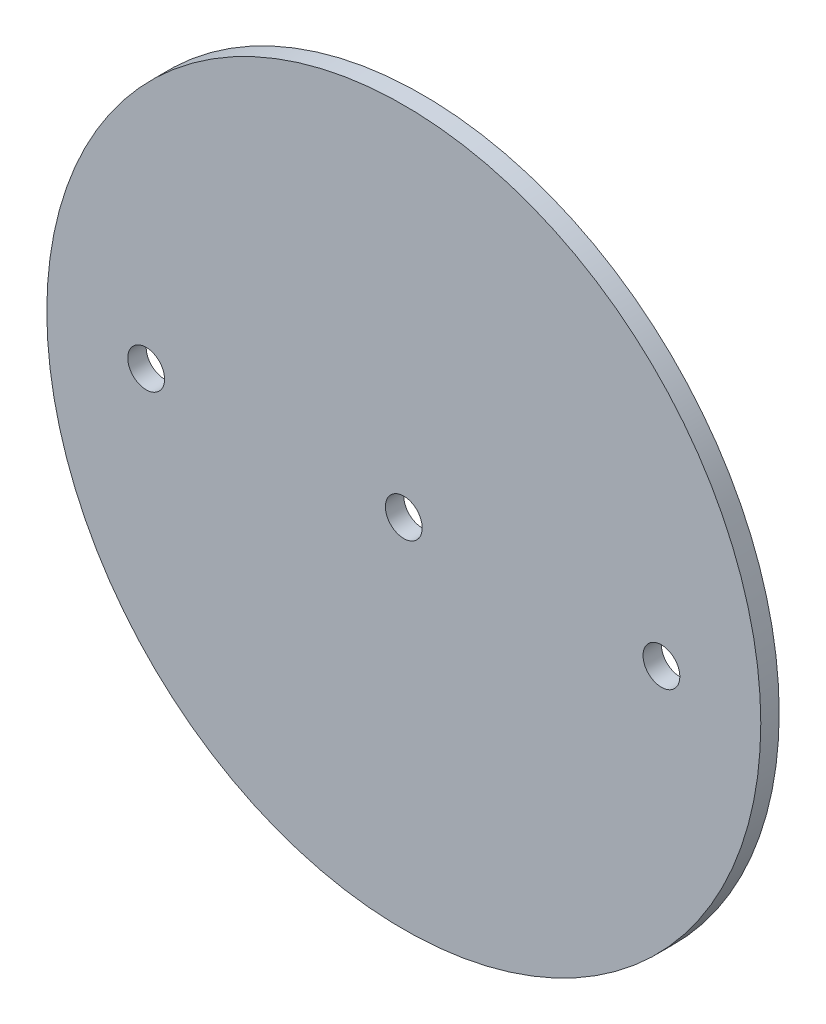
SolidWorks part; units mm, degrees
ref_plane "Front Plane" through (0, 0, 0) normal (0, 0, 1) x (1, 0, 0)
ref_plane "Top Plane" through (0, 0, 0) normal (0, 1, 0) x (1, 0, 0)
ref_plane "Right Plane" through (0, 0, 0) normal (1, 0, 0) x (0, 0, -1)
sketch "Sketch1" plane through (0, 0, 0) normal (0, 0, 1) x (1, 0, 0)
  circle A0 centre (0, 0) radius 61.595
  dimension "D1" = 123.19
extrude "Boss-Extrude1" add sketch "Sketch1" along normal mid plane 3.175
sketch "Sketch2" plane through (0, 0, 1.5875) normal (0, 0, 1) x (1, 0, 0)
  line L0 (-1000, 0) -> (49000, 0) construction
  point P1 (0, 0)
  point P4 (44.45, 0)
  point P5 (-44.45, 0)
  dimension "D1" = 44.45
  dimension "D2" = 88.9
hole_wizard "1/4 (0.25) Diameter Hole1" positions "Sketch2" profile "Sketch3" hole size "1/4" standard "ANSI Inch" end condition through all
sketch "Sketch3" plane through (-44.45, 0, 1.5875) normal (1, 0, 0) x (0, -1, 0)
  line L0 (0, 0) -> (0, 3.175)
  line L1 (0, 3.175) -> (3.175, 3.175)
  line L2 (3.175, 3.175) -> (3.175, 0)
  line L5 (3.175, 0) -> (0, 0)
  line L11 (0, -6.35) -> (0, 107.95) construction
  dimension "Thru Hole Dia." = 6.35
  dimension "Thru Hole Depth" = 3.175
equation "\"AIRFRAME_OD\"= 5.15in"
equation "\"AIRFRAME_ID\"= 4.99in"
equation "\"FLAT_T\"= 0.125in"
equation "\"NOSE_EXP_L\"= 27in"
equation "\"NOSE_SHOULDER_L\"= 5in"
equation "\"MAIN_L\"= 30in"
equation "\"RECO_COUP_L\"= 10in"
equation "\"RECO_SWITCH_L\"= 2in"
equation "\"DROGUE_L\"= 20in"
equation "\"ATS_FORE_COUP_L\"= 5.5in"
equation "\"ATS_AFT_COUP_L\"= 4.5in"
equation "\"LOWER_L\"= 30in"
equation "\"FIN_N\"= 4"
equation "\"CR_AFT_X\"= 0.5in"
equation "\"CR_FORE_X\"= 9.25in"
equation "\"FIN_ROOT\"= 8in"
equation "\"FIN_X\"= 0.75in"
equation "\"MOTOR_OD\"= 3.091in"
equation "\"MOTOR_ID\"= 3.00in"
equation "\"COUPLER_OD\"= 4.998in"
equation "\"COUPLER_ID\"= 4.85in"
equation "\"D1@Sketch1\"=\"COUPLER_ID\""
equation "\"D1@Boss-Extrude1\"=\"FLAT_T\""
equation "\"RECO_ROD_X\"= 3.5in"
equation "\"ATS_ROD_X\"= 3.75in"
equation "\"D1@Sketch2\"=\"RECO_ROD_X\"*0.5"
equation "\"D2@Sketch2\"=\"RECO_ROD_X\""
equation "\"MOTOR_L\"= 14in"
equation "\"MOTOR_LOWER_X\"= 2in"
